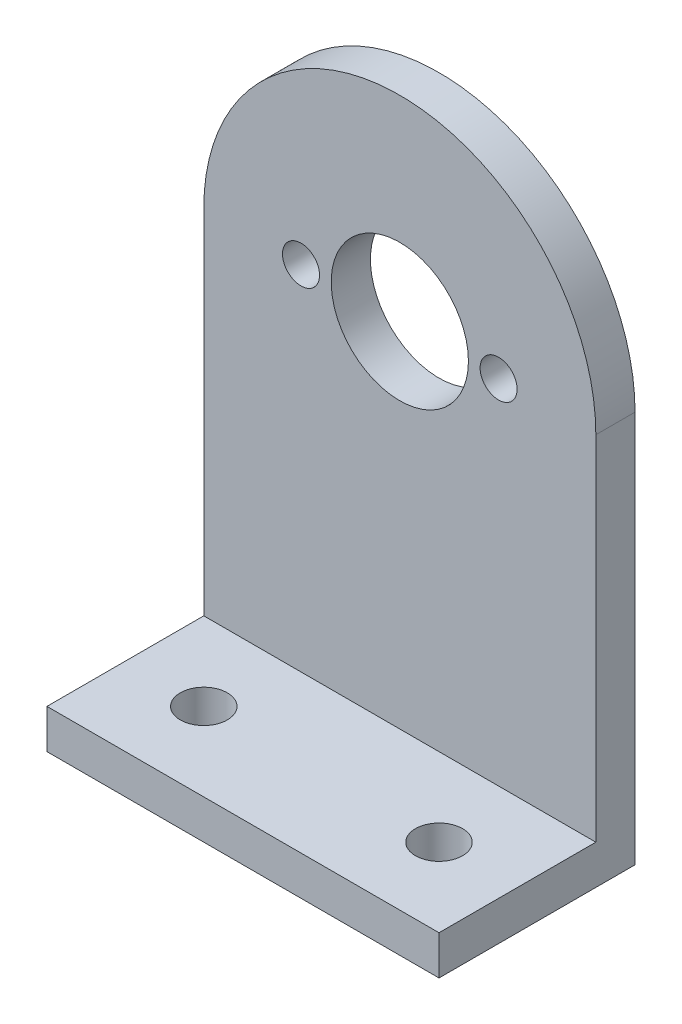
SolidWorks part; units mm, degrees
ref_plane "Front Plane" through (0, 0, 0) normal (0, 0, 1) x (1, 0, 0)
ref_plane "Top Plane" through (0, 0, 0) normal (0, 1, 0) x (1, 0, 0)
ref_plane "Right Plane" through (0, 0, 0) normal (1, 0, 0) x (0, 0, -1)
sketch "Sketch1" plane through (0, 0, 0) normal (0, 0, 1) x (1, 0, 0)
  line L1 (-15.875, 0) -> (15.875, 0)
  line L2 (-15.875, 0) -> (-15.875, -31.75)
  line L3 (-15.875, -31.75) -> (15.875, -31.75)
  line L4 (15.875, 0) -> (15.875, -31.75)
  circle A0 centre (0, 0) radius 15.875
  arc A2 (-15.875, 0) -> (15.875, 0) centre (0, 0) ccw
  dimension "D1" = 31.75
  dimension "D2" = 31.75
extrude "Boss-Extrude1" add sketch "Sketch1" along normal blind 3.175 contours A0 | L2 L1 L4 L3
sketch "Sketch3" plane through (0, 0, 3.175) normal (0, 0, 1) x (1, 0, 0)
  circle A0 centre (0, 0) radius 5.5562
  dimension "D1" = 11.1125
extrude "Cut-Extrude1" cut sketch "Sketch3" against normal through all
sketch "Sketch4" plane through (0, 0, 3.175) normal (0, 0, 1) x (1, 0, 0)
  line L0 (15.875, 0) -> (15.875, -31.75) construction
  line L1 (-15.875, -31.75) -> (15.875, -31.75)
  line L2 (-15.875, -31.75) -> (-15.875, -28.575)
  line L3 (-15.875, -28.575) -> (15.875, -28.575)
  line L4 (15.875, -31.75) -> (15.875, -28.575)
  dimension "D1" = 3.175
extrude "Boss-Extrude2" add sketch "Sketch4" along normal blind 12.7
sketch "Sketch5" plane through (0, -28.575, 0) normal (0, 1, 0) x (1, 0, 0)
  line L0 (-15.875, -9.525) -> (15.875, -9.525) construction
  line L1 (-15.875, -15.875) -> (-15.875, -3.175) construction
  line L2 (15.875, -15.875) -> (15.875, -3.175) construction
  line L3 (0, -3.175) -> (0, -15.875) construction
  line L4 (15.875, -3.175) -> (-15.875, -3.175) construction
  line L5 (15.875, -15.875) -> (-15.875, -15.875) construction
  circle A0 centre (-9.525, -9.525) radius 1.905
  circle A1 centre (9.525, -9.525) radius 1.905
  dimension "D1" = 3.81
  dimension "D2" = 9.525
extrude "Cut-Extrude2" cut sketch "Sketch5" against normal through all
hole_wizard "Ø3.0mm Dowel Hole1" positions "Sketch8" profile "Sketch9" hole size "Ø3.0" standard "ANSI Metric" end condition through all
sketch "Sketch8" plane through (0, 0, 3.175) normal (0, 0, 1) x (1, 0, 0)
  line L0 (-15.875, 0) -> (15.875, 0) construction
  point P0 (-8.001, 0)
  point P2 (8.001, 0)
  dimension "D1" = 16.002
  dimension "D2" = 8.001
sketch "Sketch9" plane through (-8.001, 0, 3.175) normal (1, 0, 0) x (0, -1, 0)
  line L0 (0, 0) -> (0, 3.175)
  line L1 (0, 3.175) -> (1.5, 3.175)
  line L2 (1.5, 3.175) -> (1.5, 0)
  line L5 (1.5, 0) -> (0, 0)
  line L11 (0, -6.35) -> (0, 107.95) construction
  dimension "Thru Hole Dia." = 3
  dimension "Thru Hole Depth" = 3.175
chamfer "Chamfer1" distance 0.762 angle 45 2 edges at (-6.501, 0, 0) (9.501, 0, 0)
